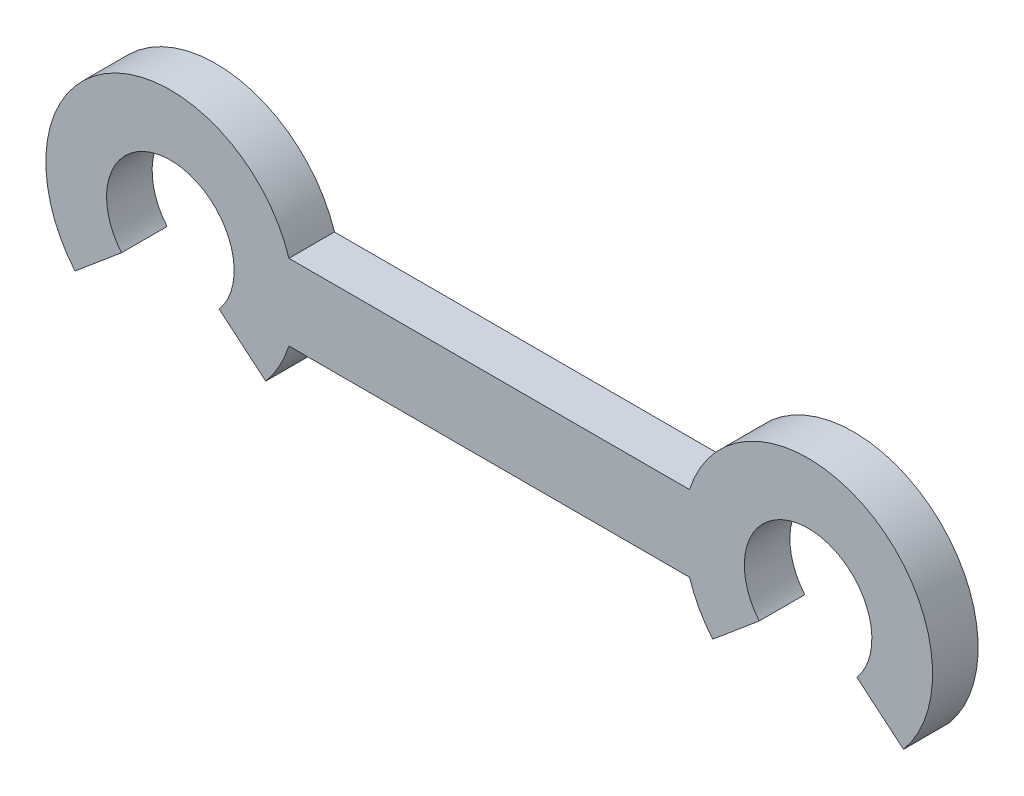
SolidWorks part; units mm, degrees
ref_plane "Plan de face" through (0, 0, 0) normal (0, 0, 1) x (1, 0, 0)
ref_plane "Plan de dessus" through (0, 0, 0) normal (0, 1, 0) x (1, 0, 0)
ref_plane "Plan de droite" through (0, 0, 0) normal (1, 0, 0) x (0, 0, -1)
sketch "Esquisse1" plane through (0, 0, 0) normal (0, 0, 1) x (1, 0, 0)
  line L0 (-10.5, 0) -> (-4.7397, -4.8335)
  line L1 (-10.5, -1.25) -> (10.5, -1.25)
  line L2 (-10.5, -1.25) -> (-10.5, 1.25)
  line L3 (-10.5, 1.25) -> (10.5, 1.25)
  line L4 (10.5, -1.25) -> (10.5, 1.25)
  line L5 (-10.5, -1.25) -> (10.5, 1.25) construction
  line L6 (-10.5, 1.25) -> (10.5, -1.25) construction
  line L7 (-10.5, 0) -> (-16.2603, -4.8335)
  line L8 (10.5, 0) -> (4.36, -5.1521)
  line L9 (10.5, 0) -> (16.64, -5.1521)
  circle A0 centre (10.5, 0) radius 2.1
  circle A1 centre (10.5, 0) radius 4.1
  circle A2 centre (-10.5, 0) radius 2.1
  circle A3 centre (-10.5, 0) radius 4.1
  point P0 (0, 0)
  point P12 (0, 0)
  point P17 (-16.2603, -4.8335)
  point P18 (4.36, -5.1521)
  dimension "D3" = 4.2
  dimension "D4" = 2
  dimension "D5" = 4.2
  dimension "D6" = 2
  dimension "D1" = 21
  dimension "D2" = 2.5
  dimension "D7" = 100
  dimension "D8" = 100
extrude "Boss.-Extru.1" add sketch "Esquisse1" along normal blind 1.5 contours L3 A3 L7 A2 | L1 A3 L3 A2 | A3 L1 A1 L3 | L3 A1 L1 A0 | L9 A1 L3 A0 | L0 A3 L1 A2 | L1 A1 L8 A0 region at (-12.942, -1.9125, 0) region at (-7.6149, -1.7257, 0) region at (-7.5007, 0, 0) region at (0, 0, 0) region at (7.5007, 0, 0) region at (7.6149, -1.7257, 0) region at (11.1164, 3.9475, 0)
